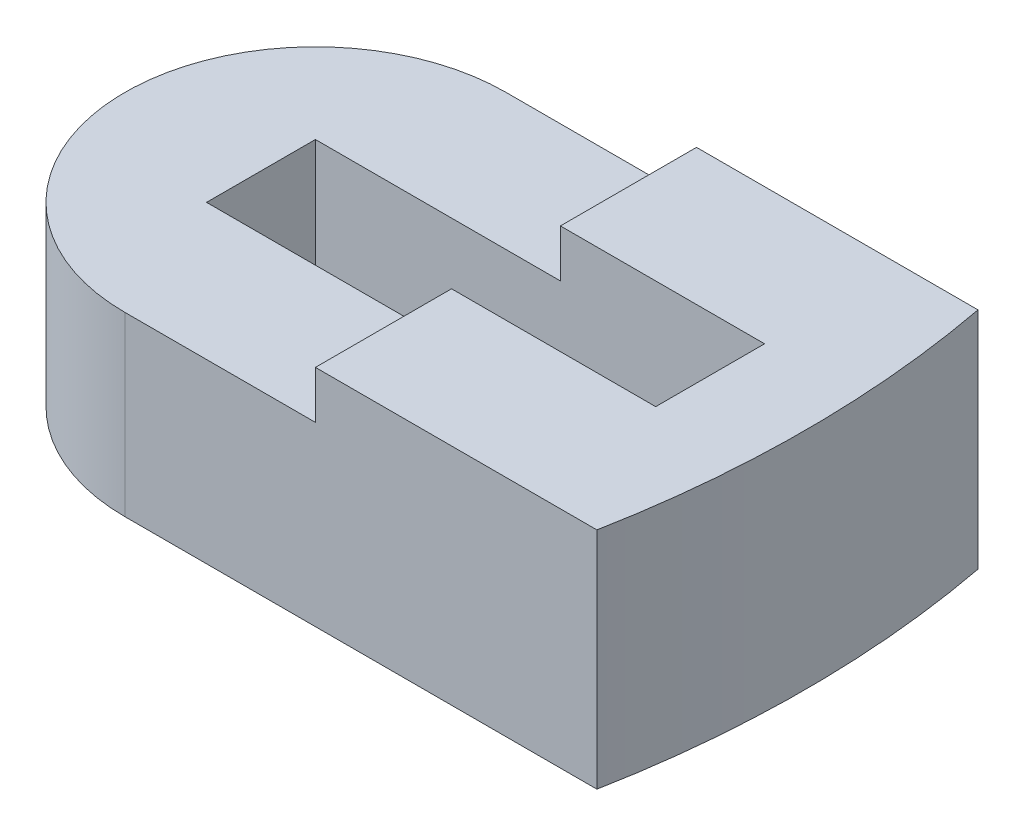
SolidWorks part; units mm, degrees
ref_plane "Front Plane" through (0, 0, 0) normal (0, 0, 1) x (1, 0, 0)
ref_plane "Top Plane" through (0, 0, 0) normal (0, 1, 0) x (1, 0, 0)
ref_plane "Right Plane" through (0, 0, 0) normal (1, 0, 0) x (0, 0, -1)
sketch "Sketch1" plane through (0, 0, 0) normal (0, 1, 0) x (1, 0, 0)
  line L0 (-9.6282, 0) -> (65.3718, 0)
  line L1 (29.3718, -14) -> (64.0536, -14)
  line L2 (29.3718, 14) -> (64.0536, 14)
  line L3 (25.3718, 0) -> (25.3718, 4)
  line L4 (25.3718, 0) -> (58.3718, 0)
  line L5 (25.3718, 4) -> (58.3718, 4)
  line L6 (58.3718, 0) -> (58.3718, 4)
  line L7 (58.3718, 0) -> (25.3718, 0)
  line L8 (58.3718, 0) -> (58.3718, -4)
  line L9 (25.3718, 0) -> (25.3718, -4)
  line L10 (58.3718, -4) -> (25.3718, -4)
  line L11 (43.3718, 14) -> (43.3718, -14)
  circle A0 centre (-9.6282, 0) radius 75
  circle A1 centre (29.3718, 0) radius 14
  dimension "D1" = 36
  dimension "D2" = 7
  dimension "D3" = 4
  dimension "D4" = 4
  dimension "D5" = 4
extrude "Boss-Extrude1" add sketch "Sketch1" along normal blind 3 contours A1 L11 L5 | A1 L10 L11 | L0 A1 L5 L3 | L10 A1 L0 L9 | L5 L11 L7 L6 | L7 L11 L10 L8 region at (34.2762, 0, -1.9891) region at (34.2762, 0, 1.9891) region at (50.8718, 0, -2) region at (43.1974, 0, -3.0042) region at (50.8718, 0, 2) region at (43.1974, 0, 3.0042)
extrude "Boss-Extrude2" add sketch "Sketch1<6>" along normal blind 16.5 contours L0 A0 L2 L11 L5 L6 | L1 A0 L0 L8 L10 L11 region at (54.9713, 0, -8.1515) region at (54.9713, 0, 8.1515)
sketch "Sketch1<6>" plane through (0, 0, 0) normal (0, 1, 0) x (1, 0, 0) same geometry as "Sketch1"
extrude "Boss-Extrude3" add sketch "Sketch1<7>" along normal blind 13 contours A1 L5 L11 L2 | L5 A1 L0 L3 | A1 L1 L11 L10 | A1 L10 L9 L0 region at (27.8956, 0, 7.1315) region at (27.8956, 0, -7.1315) region at (40.1895, 0, -11.0199) region at (40.1895, 0, 11.0199)
sketch "Sketch1<7>" plane through (0, 0, 0) normal (0, 1, 0) x (1, 0, 0) same geometry as "Sketch1"
